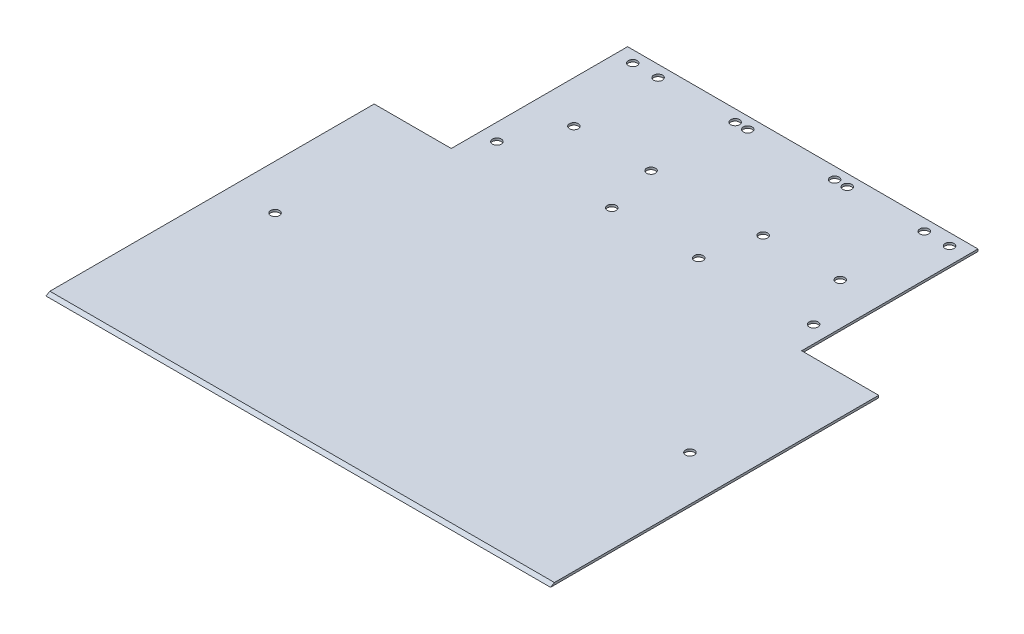
SolidWorks part; units mm, degrees
ref_plane "Alzado" through (0, 0, 0) normal (0, 0, 1) x (1, 0, 0)
ref_plane "Planta" through (0, 0, 0) normal (0, 1, 0) x (1, 0, 0)
ref_plane "Vista lateral" through (0, 0, 0) normal (1, 0, 0) x (0, 0, -1)
sketch "Croquis1" plane through (0, 0, 0) normal (0, 1, 0) x (1, 0, 0)
  line L0 (-62.5, 90) -> (-62.5, 27.08)
  line L1 (90, -90) -> (-90, -90)
  line L2 (90, -90) -> (90, 27.08)
  line L3 (62.5, 90) -> (-62.5, 90)
  line L4 (-90, -90) -> (-90, 27.08)
  line L5 (90, -90) -> (-62.5, 62.5) construction
  line L6 (62.5, 62.5) -> (-90, -90) construction
  line L7 (-62.5, 27.08) -> (-90, 27.08)
  line L8 (0, 90) -> (0, -90) construction
  line L9 (62.5, 27.08) -> (90, 27.08)
  line L10 (62.5, 90) -> (62.5, 27.08)
  point P0 (0, 0)
  dimension "D1" = 125
  dimension "D2" = 180
  dimension "D3" = 27.5
  dimension "D4" = 62.92
  dimension "D5" = 27.5
extrude "Saliente-Extruir1" add sketch "Croquis1" along normal blind 0.8
sketch "Croquis2" plane through (-90, 0, 0) normal (-1, 0, 0) x (0, 0, 1)
  line L0 (90, 0) -> (88.6144, 0.8)
  line L1 (-27.08, 0.8) -> (90, 0.8) construction
  line L2 (88.6144, 0.8) -> (90, 0.8)
  line L3 (90, 0.8) -> (90, 0)
  dimension "D1" = 60
extrude "Cortar-Extruir1" cut sketch "Croquis2" against normal up to next
sketch "Croquis3" plane through (0, 0.8, 0) normal (0, 1, 0) x (1, 0, 0)
  circle A0 centre (74, -24.2793) radius 1.585
extrude "Cortar-Extruir2" cut sketch "Croquis3" against normal up to next
mirror "Simetría1" about plane through (0, 0, 0) normal (1, 0, 0) of "Cortar-Extruir2"
sketch "Croquis4" plane through (0, 0.8, 0) normal (0, 1, 0) x (1, 0, 0)
  circle A0 centre (-56.5, 37.3511) radius 1.585
  circle A1 centre (-15.5, 37.3511) radius 1.585
  circle A2 centre (-15.5, 85.8511) radius 1.585
  circle A3 centre (-56.5, 85.8511) radius 1.585
extrude "Cortar-Extruir3" cut sketch "Croquis4" against normal up to next
sketch "Croquis6" plane through (0, 0.8, 0) normal (0, 1, 0) x (1, 0, 0)
  circle A0 centre (56.5, 85.8511) radius 1.585
  circle A1 centre (15.5, 85.8511) radius 1.585
  circle A2 centre (15.5, 37.3511) radius 1.585
  circle A3 centre (56.5, 37.3511) radius 1.585
extrude "Cortar-Extruir4" cut sketch "Croquis6" against normal up to next
sketch "Croquis7" plane through (0, 0.8, 0) normal (0, 1, 0) x (1, 0, 0)
  circle A0 centre (-20, 85.8511) radius 1.585
  circle A1 centre (-47.5, 85.8511) radius 1.585
  circle A2 centre (-47.5, 55.8511) radius 1.585
  circle A3 centre (-20, 55.8511) radius 1.585
extrude "Cortar-Extruir5" cut sketch "Croquis7" against normal up to next
mirror "Simetría2" about plane through (0, 0, 0) normal (1, 0, 0) of "Cortar-Extruir5"
